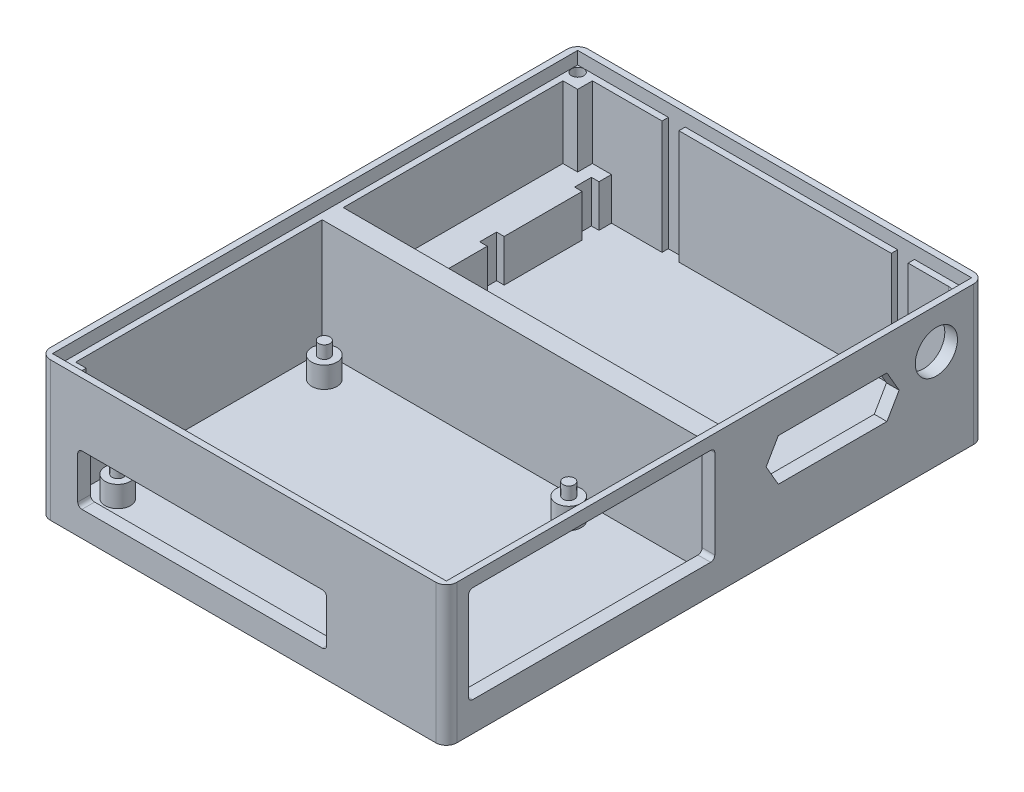
SolidWorks part; units mm, degrees
ref_plane "Front Plane" through (0, 0, 0) normal (0, 0, 1) x (1, 0, 0)
ref_plane "Top Plane" through (0, 0, 0) normal (0, 1, 0) x (1, 0, 0)
ref_plane "Right Plane" through (0, 0, 0) normal (1, 0, 0) x (0, 0, -1)
sketch "Sketch1" plane through (0, 0, 0) normal (0, 1, 0) x (1, 0, 0)
  line L1 (-82.5, -77.9) -> (82.5, -77.9)
  line L2 (-82.5, -77.9) -> (-82.5, 77.9)
  line L3 (-82.5, 77.9) -> (82.5, 77.9)
  line L4 (82.5, -77.9) -> (82.5, 77.9)
  line L5 (-82.5, -77.9) -> (82.5, 77.9) construction
  line L6 (-82.5, 77.9) -> (82.5, -77.9) construction
  point P0 (0, 0)
  dimension "D1" = 155.8
  dimension "D2" = 165
extrude "Boss-Extrude1" add sketch "Sketch1" along normal blind 3
sketch "Sketch2" plane through (0, 3, 0) normal (0, 1, 0) x (1, 0, 0)
  circle A0 centre (1.05, -25.4) radius 3
  circle A1 centre (1.05, -25.4) radius 1.35
  point P0 (1.05, -25.4)
  point P1 (59.05, -74.4)
  point P3 (1.05, -74.4)
  point P4 (59.05, -25.4)
extrude "Boss-Extrude2" add sketch "Sketch2" along normal blind 5 contours A0 A1 region at (-1.8651, 3, 25.4)
sketch "Sketch5" plane through (0, 3, 0) normal (0, 1, 0) x (1, 0, 0)
  circle A0 centre (1.05, -25.4) radius 1.35 construction
  ellipse E0 centre (1.05, -25.4) end of major axis (2.4, -25.4) minor radius 1.35
extrude "Boss-Extrude3" add sketch "Sketch5" along normal blind 8
pattern_sketch "Sketch-Pattern1" of "Boss-Extrude2", "Boss-Extrude3" driven by "Sketch2"
sketch "Sketch6" plane through (82.5, 0, 0) normal (1, 0, 0) x (0, 0, -1)
  line L1 (-77.9, 3) -> (77.9, 3)
  line L2 (-77.9, 3) -> (-77.9, 0)
  line L3 (-77.9, 0) -> (77.9, 0)
  line L4 (77.9, 3) -> (77.9, 0)
extrude "Boss-Extrude4" add sketch "Sketch6" along normal blind 3
sketch "Sketch7" plane through (0, 3, 0) normal (0, 1, 0) x (1, 0, 0)
  line L0 (-82.5, -77.9) -> (85.5, -77.9) construction
  line L1 (-82.5, 77.9) -> (-7.95, 77.9)
  line L2 (-82.5, 77.9) -> (-82.5, -77.9)
  line L3 (-82.5, -77.9) -> (-7.95, -77.9)
  line L4 (-7.95, 77.9) -> (-7.95, -77.9)
  circle A0 centre (1.05, -74.4) radius 3 construction
  dimension "D1" = 9
extrude "Cut-Extrude1" cut sketch "Sketch7" against normal blind 3
sketch "Sketch11" plane through (0, 3, 0) normal (0, 1, 0) x (1, 0, 0)
  line L0 (85.5, 77.9) -> (85.5, -77.9) construction
  line L1 (-7.95, 77.9) -> (85.5, 77.9)
  line L2 (-7.95, 77.9) -> (-7.95, 43.71)
  line L3 (-7.95, 43.71) -> (85.5, 43.71)
  line L4 (85.5, 77.9) -> (85.5, 43.71)
extrude "Cut-Extrude2" cut sketch "Sketch11" against normal blind 3
sketch "Sketch12" plane through (85.5, 0, 0) normal (1, 0, 0) x (0, 0, -1)
  line L1 (-77.9, 3) -> (43.71, 3)
  line L2 (-77.9, 3) -> (-77.9, 0)
  line L3 (-77.9, 0) -> (43.71, 0)
  line L4 (43.71, 3) -> (43.71, 0)
extrude "Boss-Extrude5" add sketch "Sketch12" along normal blind 3
sketch "Sketch13" plane through (0, 0, 77.9) normal (0, 0, 1) x (1, 0, 0)
  line L1 (-7.95, 3) -> (88.5, 3)
  line L2 (-7.95, 3) -> (-7.95, 0)
  line L3 (-7.95, 0) -> (88.5, 0)
  line L4 (88.5, 3) -> (88.5, 0)
extrude "Boss-Extrude6" add sketch "Sketch13" along normal blind 6
sketch "Sketch14" plane through (0, 3, 0) normal (0, 1, 0) x (1, 0, 0)
  line L0 (-7.95, 43.71) -> (88.5, 43.71) construction
  line L1 (-4.95, 40.71) -> (85.5, 40.71)
  line L2 (-4.95, 40.71) -> (-4.95, -80.9)
  line L3 (-4.95, -80.9) -> (85.5, -80.9)
  line L4 (85.5, 40.71) -> (85.5, -80.9)
  line L5 (-7.95, -83.9) -> (-7.95, 43.71) construction
  line L6 (88.5, 43.71) -> (88.5, -83.9) construction
  line L7 (88.5, -83.9) -> (-7.95, -83.9) construction
  line L9 (-7.95, -83.9) -> (88.5, -83.9)
  line L10 (-7.95, -83.9) -> (-7.95, 43.71)
  line L11 (-7.95, 43.71) -> (88.5, 43.71)
  line L12 (88.5, -83.9) -> (88.5, 43.71)
  dimension "D1" = 3
  dimension "D2" = 3
  dimension "D3" = 3
  dimension "D4" = 3
extrude "Boss-Extrude8" add sketch "Sketch14" along normal blind 30
sketch "Sketch15" plane through (85.5, 0, 0) normal (-1, 0, 0) x (0, 0, 1)
  line L0 (80.9, 33) -> (-40.71, 33) construction
  line L1 (20.2077, 30) -> (78.6284, 30)
  line L2 (20.2077, 30) -> (20.2077, 7)
  line L3 (20.2077, 7) -> (78.6284, 7)
  line L4 (78.6284, 30) -> (78.6284, 7)
  line L5 (80.9, 3) -> (-40.71, 3) construction
  dimension "D1" = 3
  dimension "D2" = 4
extrude "Cut-Extrude3" cut sketch "Sketch15" against normal blind 30
sketch "Sketch16" plane through (0, 0, 80.9) normal (0, 0, -1) x (-1, 0, 0)
  line L0 (7.95, 33) -> (-88.5, 33) construction
  line L1 (-60.0886, 18) -> (-1.05, 18)
  line L2 (-60.0886, 18) -> (-60.0886, 6)
  line L3 (-60.0886, 6) -> (-1.05, 6)
  line L4 (-1.05, 18) -> (-1.05, 6)
  line L5 (4.95, 33) -> (4.95, 3) construction
  dimension "D1" = 12
  dimension "D2" = 15
  dimension "D3" = 6
extrude "Cut-Extrude4" cut sketch "Sketch16" against normal blind 30
sketch "Sketch17" plane through (0, 33, 0) normal (0, 1, 0) x (1, 0, 0)
  line L0 (88.5, 43.71) -> (-7.95, 43.71) construction
  line L1 (-6.45, 42.21) -> (87, 42.21)
  line L2 (-6.45, 42.21) -> (-6.45, -82.4)
  line L3 (-6.45, -82.4) -> (87, -82.4)
  line L4 (87, 42.21) -> (87, -82.4)
  line L5 (-7.95, 43.71) -> (-7.95, -83.9) construction
  line L6 (88.5, -83.9) -> (88.5, 43.71) construction
  line L7 (-7.95, -83.9) -> (88.5, -83.9) construction
  dimension "D1" = 1.5
  dimension "D2" = 1.5
  dimension "D3" = 1.5
  dimension "D4" = 1.5
extrude "Cut-Extrude5" cut sketch "Sketch17" against normal blind 3
sketch "Sketch19" plane through (85.5, 0, 0) normal (-1, 0, 0) x (0, 0, 1)
  line L0 (2.25, 20) -> (-17.75, 20) construction
  line L1 (83.9, 33) -> (-43.71, 33) construction
  line L5 (-14.8632, 25) -> (-20.6368, 25)
  line L6 (-20.6368, 25) -> (-23.5235, 20)
  line L7 (-23.5235, 20) -> (-20.6368, 15)
  line L8 (-20.6368, 15) -> (-14.8632, 15)
  line L10 (8.0235, 20) -> (5.1368, 25)
  line L11 (5.1368, 25) -> (-0.6368, 25)
  line L14 (-0.6368, 15) -> (5.1368, 15)
  line L15 (5.1368, 15) -> (8.0235, 20)
  line L21 (-0.6368, 25) -> (-14.8632, 25)
  line L22 (-14.8632, 15) -> (-0.6368, 15)
  line L24 (-0.6368, 25) -> (-2.0801, 22.5) [skipped]
  line L25 (-11.9043, 19.875) -> (-13.3477, 22.375) [skipped]
  line L26 (-14.8632, 15) -> (-13.4199, 17.5) [skipped]
  line L27 (-3.5235, 20) -> (-2.0801, 17.5) [skipped]
  arc A0 (-17.75, 25) -> (-17.75, 15) centre (-17.75, 20) ccw construction
  arc A1 (2.25, 15) -> (2.25, 25) centre (2.25, 20) ccw construction
  dimension "D1" = 20
  dimension "D2" = 10
  dimension "D3" = 13
extrude "Cut-Extrude6" cut sketch "Sketch19" against normal blind 3
fillet "Fillet1" radius 2.5 1 edges at (-7.95, 16.5, 83.9) type face fillet first side face at (30.5693, 12, 83.9) second side face at (-7.95, 16.5, 20.095)
fillet "Fillet3" radius 2.5 1 edges at (88.5, 16.5, 83.9) type face fillet first side face at (30.5693, 12, 83.9) second side face at (88.5, 20, -7.75)
fillet "Fillet4" radius 2.5 1 edges at (88.5, 16.5, -43.71) type face fillet first side face at (88.5, 20, -7.75) second side face at (40.275, 16.5, -43.71)
fillet "Fillet5" radius 2.5 1 edges at (-7.95, 16.5, -43.71) type face fillet first side face at (39.025, 16.5, -43.71) second side face at (-7.95, 16.5, 18.845)
fillet "Fillet6" radius 2.5 1 edges at (85.5, 16.5, -40.71) type face fillet first side face at (40.275, 16.5, -40.71) second side face at (85.5, 20, -7.75)
fillet "Fillet7" radius 2.5 1 edges at (-4.95, 16.5, -40.71) type face fillet first side face at (-4.95, 16.5, 20.095) second side face at (39.025, 16.5, -40.71)
fillet "Fillet8" radius 2.5 1 edges at (-4.95, 16.5, 80.9) type face fillet first side face at (30.5693, 12, 80.9) second side face at (-4.95, 16.5, 21.345)
fillet "Fillet9" radius 2.5 1 edges at (85.5, 16.5, 80.9) type face fillet first side face at (85.5, 20, -7.75) second side face at (30.5693, 12, 80.9)
fillet "Fillet10" radius 1 1 edges at (87.75, 30, 78.6284) type face fillet first side face at (86.9958, 20.8, 78.6284) second side face at (87.75, 30, 49.4181)
fillet "Fillet11" radius 1 1 edges at (87.75, 30, 20.2077) type face fillet first side face at (87, 20.8, 20.2077) second side face at (87.75, 30, 48.9181)
fillet "Fillet12" radius 1 1 edges at (87, 7, 20.2077) type face fillet first side face at (86.6984, 7, 55.2145) second side face at (87, 18, 20.2077)
fillet "Fillet13" radius 1 1 edges at (86.9948, 7, 78.6284) type face fillet first side face at (86.6984, 7, 55.6145) second side face at (86.9948, 18, 78.6284)
fillet "Fillet14" radius 1 1 edges at (1.05, 18, 82.4) type face fillet first side face at (1.05, 12, 82.4) second side face at (30.5693, 18, 82.4)
fillet "Fillet15" radius 1 1 edges at (60.0886, 6, 82.4) type face fillet first side face at (30.5693, 6, 82.4) second side face at (60.0886, 12, 82.4)
fillet "Fillet16" radius 1 1 edges at (60.0886, 18, 82.4) type face fillet first side face at (31.0693, 18, 82.4) second side face at (60.0886, 12.5, 82.4)
fillet "Fillet17" radius 1 1 edges at (1.05, 6, 82.4) type face fillet first side face at (1.05, 11.5, 82.4) second side face at (30.0693, 6, 82.4)
ref_plane "Plane1" through (-7.95, 33, 81.4) normal (0, 0, 1) x (1, 0, 0)
sketch "Sketch21" plane through (0, 33, 0) normal (0, 1, 0) x (1, 0, 0)
  line L1 (-6.45, -82.4) -> (87, -82.4)
  line L2 (-6.45, -82.4) -> (-6.45, 42.21)
  line L3 (-6.45, 42.21) -> (87, 42.21)
  line L4 (87, -82.4) -> (87, 42.21)
sketch "Sketch22" plane through (0, 33, 0) normal (0, 1, 0) x (1, 0, 0)
  line L3 (-7.95, -20.095) -> (88.5, -20.095) construction
  line L4 (-7.95, 41.21) -> (-7.95, -81.4) construction
  line L5 (88.5, -81.4) -> (88.5, 41.21) construction
sketch "Sketch23" plane through (88.5, 0, 0) normal (1, 0, 0) x (0, 0, -1)
  line L3 (-82.4, 33) -> (42.21, 33) construction
  circle A0 centre (32.3668, 23.5) radius 5
  dimension "D1" = 9.5
  dimension "D2" = 10
extrude "Cut-Extrude11" cut sketch "Sketch23" against normal blind 10
sketch "Sketch26" plane through (0, 3, 0) normal (0, 1, 0) x (1, 0, 0)
  line L0 (-4.95, 38.21) -> (-4.95, -78.4) construction
  line L1 (-4.95, -14.9) -> (85.5, -14.9)
  line L2 (-4.95, -14.9) -> (-4.95, -19.9)
  line L3 (-4.95, -19.9) -> (85.5, -19.9)
  line L4 (85.5, -14.9) -> (85.5, -19.9)
  line L5 (85.5, -21.2077) -> (85.5, 38.21) construction
  line L6 (3.0643, -13.9) -> (85.5, -13.9) construction
  line L7 (79.55, -21.9) -> (0.55, -21.9) construction
  dimension "D1" = 1
  dimension "D2" = 2
  dimension "D3" = 5
extrude "Boss-Extrude9" add sketch "Sketch26" along normal blind 27
sketch "Sketch27" plane through (0, 3, 0) normal (0, 1, 0) x (1, 0, 0)
  line L0 (85.5, -14.9) -> (-4.95, -14.9) construction
  line L1 (3.0643, -14.9) -> (-4.95, -14.9)
  line L3 (3.0643, 40.758) -> (-4.95, 40.758)
  line L4 (-4.95, -14.9) -> (-4.95, 40.758)
  line L20 (3.0643, 40.758) -> (3.0643, 37.758)
  line L21 (3.0643, -14.9) -> (3.0643, -11.242)
  line L22 (3.0643, 37.758) -> (1.2643, 37.758)
  line L23 (1.2643, 37.758) -> (1.2643, 33.758)
  line L24 (1.2643, 33.758) -> (3.0643, 33.758)
  line L25 (3.0643, 15.258) -> (1.2643, 15.258)
  line L26 (1.2643, 15.258) -> (1.2643, 11.258)
  line L27 (1.2643, 11.258) -> (3.0643, 11.258)
  line L28 (3.0643, 15.258) -> (3.0643, 33.758)
  line L29 (3.0643, -7.242) -> (1.2643, -7.242)
  line L30 (1.2643, -7.242) -> (1.2643, -11.242)
  line L31 (1.2643, -11.242) -> (3.0643, -11.242)
  line L32 (3.0643, -7.242) -> (3.0643, 11.258)
  dimension "D1" = 8.0143
  dimension "D2" = 4
  dimension "D3" = 1.8
  dimension "D4" = 3
  dimension "D5" = 18.5
  dimension "D6" = 18.5
  dimension "D7" = 4
extrude "Boss-Extrude10" add sketch "Sketch27" along normal blind 10
sketch "Sketch28" plane through (0, 0, -40.71) normal (0, 0, 1) x (1, 0, 0)
  line L5 (83, 30) -> (-2.45, 30) construction
  line L10 (15.0643, 30) -> (19.0643, 30)
  line L11 (15.0643, 30) -> (15.0643, 3)
  line L12 (15.0643, 3) -> (19.0643, 3)
  line L13 (19.0643, 30) -> (19.0643, 3)
  line L14 (83, 3) -> (3.0643, 3) construction
  line L16 (69.4643, 30) -> (73.4643, 30)
  line L17 (69.4643, 30) -> (69.4643, 3)
  line L18 (69.4643, 3) -> (73.4643, 3)
  line L19 (73.4643, 30) -> (73.4643, 3)
  dimension "D1" = 4
  dimension "D2" = 4
  dimension "D3" = 58.4
extrude "Cut-Extrude12" cut sketch "Sketch28" against normal blind 1.5
sketch "Sketch29" plane through (0, 13, 0) normal (0, 1, 0) x (1, 0, 0)
  line L1 (-6.45, 42.21) -> (-1.45, 42.21)
  line L2 (-6.45, 42.21) -> (-6.45, 37.21)
  line L3 (-6.45, 37.21) -> (-1.45, 37.21)
  line L4 (-1.45, 42.21) -> (-1.45, 37.21)
  dimension "D1" = 5
  dimension "D2" = 5
extrude "Boss-Extrude11" add sketch "Sketch29" along normal blind 17
sketch "Sketch30" plane through (0, 3, 0) normal (0, 1, 0) x (1, 0, 0)
  line L1 (-6.45, -82.4) -> (-2.45, -82.4)
  line L2 (-6.45, -82.4) -> (-6.45, -78.4)
  line L3 (-6.45, -78.4) -> (-2.45, -78.4)
  line L4 (-2.45, -82.4) -> (-2.45, -78.4)
extrude "Boss-Extrude12" add sketch "Sketch30" along normal blind 27
sketch "Sketch32" plane through (0, 30, 0) normal (0, 1, 0) x (1, 0, 0)
  line L0 (-6.45, 42.21) -> (-6.45, -82.4) construction
  line L1 (-6.45, -82.4) -> (87, -82.4) construction
  point P0 (-4.95, -80.9)
  dimension "D1" = 1.5
  dimension "D2" = 1.5
sketch "Sketch33" plane through (0, 30, 0) normal (0, 1, 0) x (1, 0, 0)
  line L0 (-6.45, 42.21) -> (-6.45, -82.4) construction
  line L2 (15.0643, 42.21) -> (-6.45, 42.21) construction
  point P0 (-4.95, 40.71)
  dimension "D1" = 1.5
  dimension "D2" = 1.5
hole_wizard "M2.5 Clearance Hole1" positions "3DSketch1" profile "Sketch35" hole size "M2.5" standard "ANSI Metric"
sketch3d "3DSketch1"
  point P0 (-4.95, 30, -40.71)
  point P3 (-4.95, 30, 80.9)
sketch "Sketch35" plane through (-4.95, 30, -40.71) normal (1, 0, 0) x (0, 0, 1)
  line L0 (0, 0) -> (0, 6.8712)
  line L1 (0, 6.8712) -> (1.45, 6)
  line L2 (1.45, 6) -> (1.45, 0)
  line L5 (1.45, 0) -> (0, 0)
  line L10 (0, 6.8712) -> (-1.45, 6) construction
  line L11 (0, -6.35) -> (0, 107.95) construction
  dimension "Hole Dia." = 2.9
  dimension "Hole Depth" = 6
  dimension "Drill Angle" = 118
